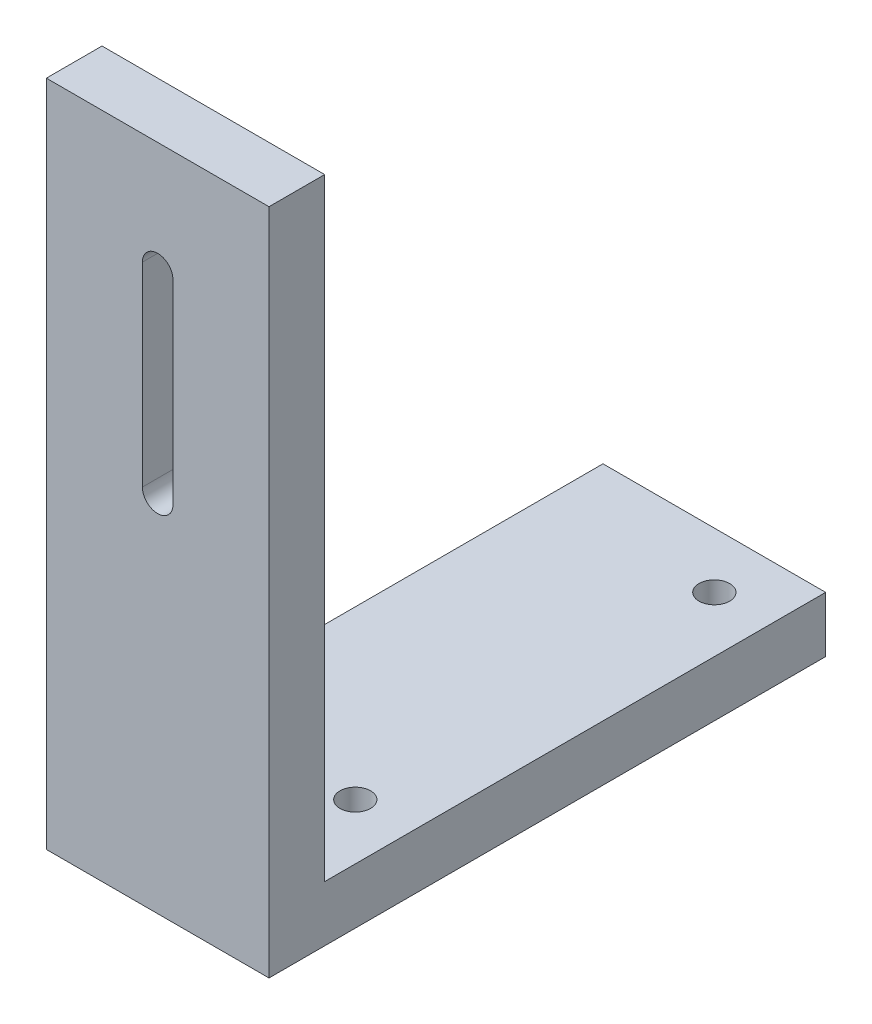
SolidWorks part; units mm, degrees
ref_plane "前基準面" through (0, 0, 0) normal (0, 0, 1) x (1, 0, 0)
ref_plane "上基準面" through (0, 0, 0) normal (0, 1, 0) x (1, 0, 0)
ref_plane "右基準面" through (0, 0, 0) normal (1, 0, 0) x (0, 0, -1)
sketch "草圖1" plane through (0, 0, 0) normal (0, 0, 1) x (1, 0, 0)
  line L1 (-23.0571, 5) -> (16.9429, 5)
  line L2 (-23.0571, 5) -> (-23.0571, -5)
  line L3 (-23.0571, -5) -> (16.9429, -5)
  line L4 (16.9429, 5) -> (16.9429, -5)
  line L5 (-23.0571, 5) -> (16.9429, -5) construction
  line L6 (-23.0571, -5) -> (16.9429, 5) construction
  point P0 (-3.0571, 0)
  dimension "D1" = 10
  dimension "D2" = 40
extrude "填料-伸長1" add sketch "草圖1" along normal blind 100
sketch "草圖3" plane through (0, 5, 0) normal (0, 1, 0) x (1, 0, 0)
  line L0 (16.9429, 0) -> (-23.0571, 0) construction
  line L1 (16.9429, -100) -> (16.9429, 0) construction
  circle A0 centre (6.9429, -10) radius 2.75
  circle A1 centre (6.9429, -74.5) radius 2.75
  dimension "D1" = 5.5
  dimension "D2" = 5.5
  dimension "D6" = 64.5
  dimension "D3" = 10
  dimension "D4" = 10
  dimension "D5" = 10
extrude "除料-伸長1" cut sketch "草圖3" against normal through all
sketch "草圖5" plane through (0, 5, 0) normal (0, 1, 0) x (1, 0, 0)
  line L0 (16.9429, -100) -> (16.9429, 0) construction
  line L1 (-23.0571, -100) -> (16.9429, -100)
  line L2 (-23.0571, -100) -> (-23.0571, -90)
  line L3 (-23.0571, -90) -> (16.9429, -90)
  line L4 (16.9429, -100) -> (16.9429, -90)
  dimension "D1" = 10
extrude "填料-伸長2" add sketch "草圖5" along normal blind 110
sketch "草圖7" plane through (0, 0, 90) normal (0, 0, -1) x (-1, 0, 0)
  line L0 (-16.9429, 5) -> (23.0571, 5) construction
  line L1 (-16.9429, 115) -> (-16.9429, 5) construction
  line L4 (5.8071, 95) -> (5.8071, 60)
  line L6 (0.3071, 95) -> (0.3071, 60)
  arc A0 (5.8071, 95) -> (0.3071, 95) centre (3.0571, 95) ccw
  arc A1 (0.3071, 60) -> (5.8071, 60) centre (3.0571, 60) ccw
  dimension "D1" = 5.5
  dimension "D2" = 5.5
  dimension "D3" = 55
  dimension "D4" = 90
  dimension "D5" = 20
  dimension "D6" = 20
extrude "除料-伸長2" cut sketch "草圖7" against normal through all
